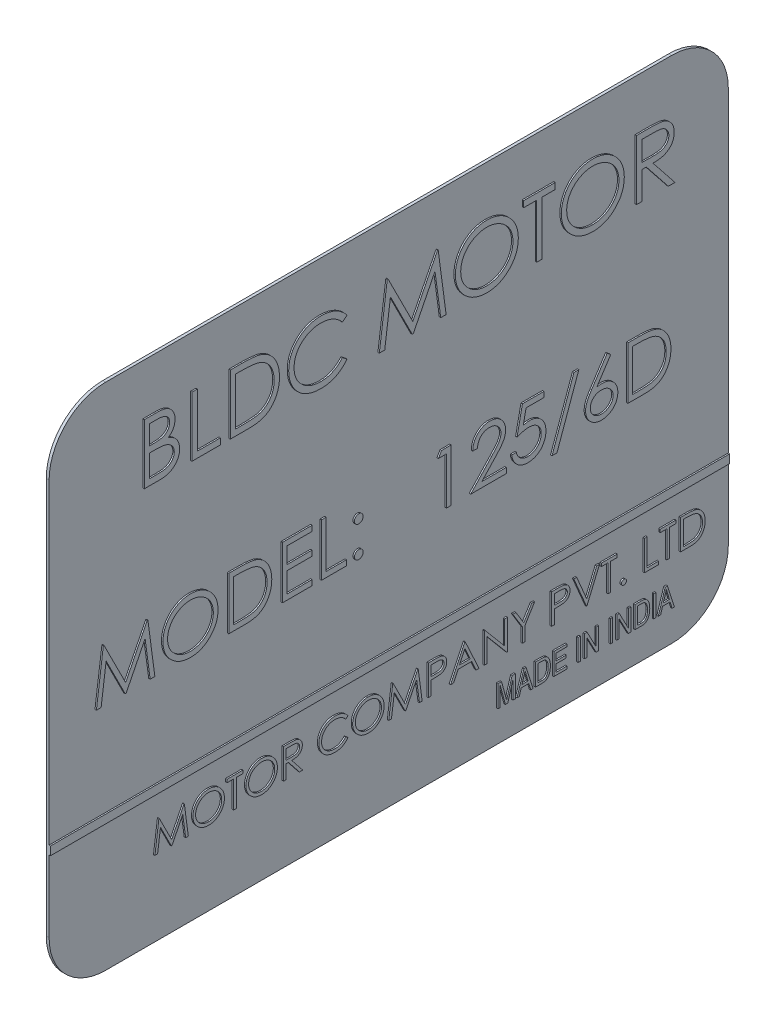
SolidWorks part; units mm, degrees
material "Stainless Steel (ferritic)"
ref_plane "Front Plane" through (0, 0, 0) normal (0, 0, 1) x (1, 0, 0)
ref_plane "Top Plane" through (0, 0, 0) normal (0, 1, 0) x (1, 0, 0)
ref_plane "Right Plane" through (0, 0, 0) normal (1, 0, 0) x (0, 0, -1)
sketch "Sketch1" plane through (0, 0, 0) normal (1, 0, 0) x (0, 0, -1)
  line L1 (2, 0) -> (22, 0)
  line L2 (0, 2) -> (0, 16)
  line L3 (2, 18) -> (22, 18)
  line L4 (24, 2) -> (24, 16)
  arc A0 (22, 0) -> (24, 2) centre (22, 2) ccw
  arc A1 (2, 0) -> (0, 2) centre (2, 2) cw
  arc A2 (0, 16) -> (2, 18) centre (2, 16) cw
  arc A3 (22, 18) -> (24, 16) centre (22, 16) cw
  point P9 (0, 0)
  dimension "D3" = 2
  dimension "D1" = 24
  dimension "D2" = 18
extrude "Boss-Extrude1" add sketch "Sketch1" along normal blind 0.1
sketch "Sketch2" plane through (0.1, 0, 0) normal (1, 0, 0) x (0, 0, -1)
  text T0 "BLDC MOTOR" font "Century Gothic" height in points 8
sketch "Sketch3" plane through (0.1, 0, 0) normal (1, 0, 0) x (0, 0, -1)
  text T0 "MODEL:   125/6D" font "Century Gothic" height in points 7
extrude "Boss-Extrude2" add sketch "Sketch2" along normal blind 0.05
extrude "Boss-Extrude3" add sketch "Sketch3" along normal blind 0.05
sketch "Sketch4" plane through (0.1, 0, 0) normal (1, 0, 0) x (0, 0, -1)
  line L0 (0, 16) -> (0, 2) construction
  line L1 (0, 4.8313) -> (24, 4.8313)
  line L2 (0, 4.8313) -> (0, 4.5313)
  line L3 (0, 4.5313) -> (24, 4.5313)
  line L4 (24, 4.8313) -> (24, 4.5313)
  line L5 (24, 2) -> (24, 16) construction
  text T2 "MOTOR COMPANY PVT. LTD" font "Century Gothic" height in points 4
  text T3 "MADE IN INDIA" font "Arial Narrow" height in points 3
  dimension "D1" = 0.3
extrude "Boss-Extrude4" add sketch "Sketch4" along normal blind 0.05
scale "Scale1" scale about centroid uniform scaling yes scale factor 2.3
